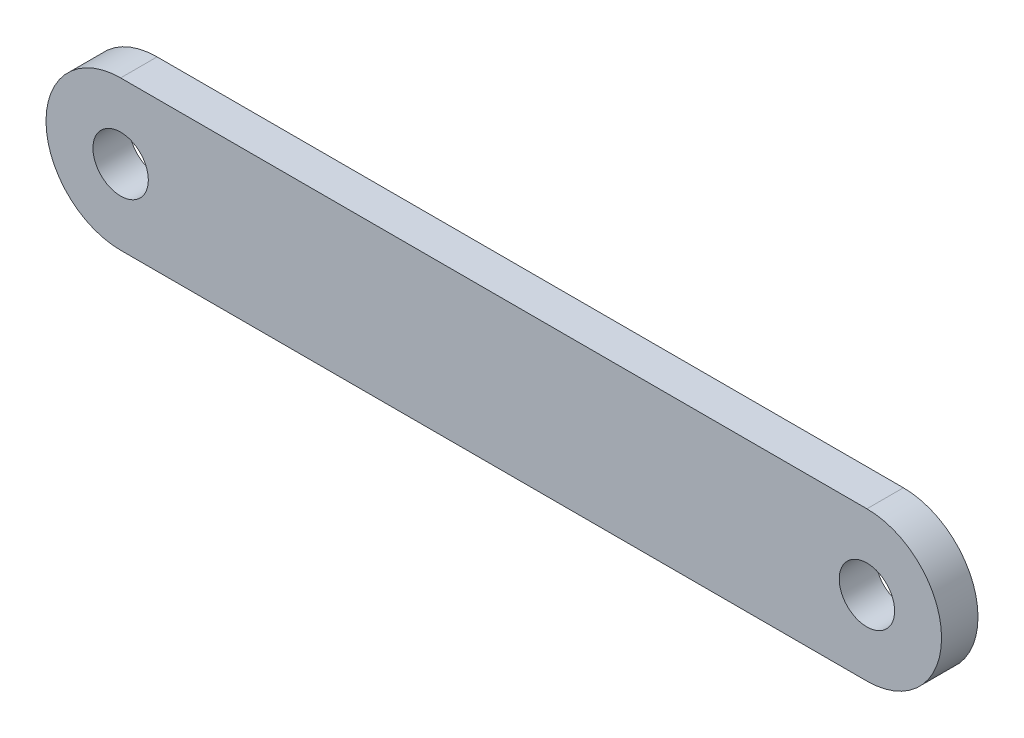
SolidWorks part; units mm, degrees
material "6061 Alloy"
ref_plane "Front Plane" through (0, 0, 0) normal (0, 0, 1) x (1, 0, 0)
ref_plane "Top Plane" through (0, 0, 0) normal (0, 1, 0) x (1, 0, 0)
ref_plane "Right Plane" through (0, 0, 0) normal (1, 0, 0) x (0, 0, -1)
sketch "Sketch1" plane through (0, 0, 0) normal (0, 0, 1) x (1, 0, 0)
  line L0 (-32.5, 0) -> (32.5, 0) construction
  line L1 (-32.5, 6.5) -> (32.5, 6.5)
  line L2 (-32.5, -6.5) -> (32.5, -6.5)
  arc A0 (-32.5, 6.5) -> (-32.5, -6.5) centre (-32.5, 0) ccw
  arc A1 (32.5, -6.5) -> (32.5, 6.5) centre (32.5, 0) ccw
  circle A2 centre (-32.5, 0) radius 2.413
  circle A3 centre (32.5, 0) radius 2.413
  point P2 (0, 0)
  dimension "D1" = 4.826
  dimension "D2" = 65
  dimension "D3" = 13
extrude "Boss-Extrude1" add sketch "Sketch1" along normal blind 3.175
